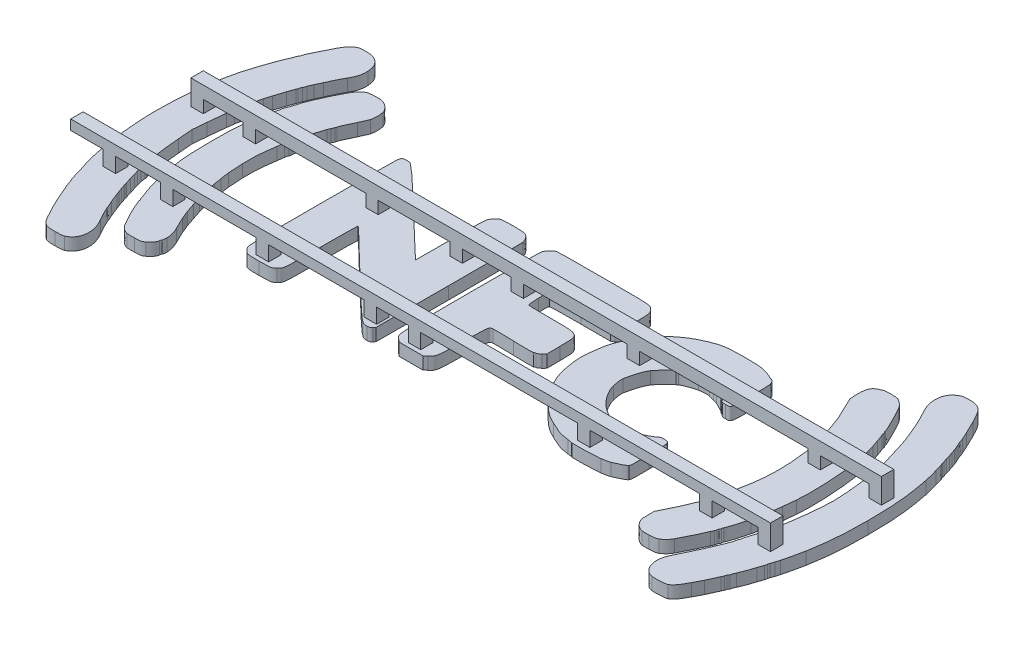
SolidWorks part; units mm, degrees
ref_plane "Front Plane" through (0, 0, 0) normal (0, 0, 1) x (1, 0, 0)
ref_plane "Top Plane" through (0, 0, 0) normal (0, 1, 0) x (1, 0, 0)
ref_plane "Right Plane" through (0, 0, 0) normal (1, 0, 0) x (0, 0, -1)
sketch "Sketch1" plane through (0, 0, 0) normal (0, 1, 0) x (1, 0, 0)
  line L0 (-25.791, 1.2525) -> (-25.8929, 0.1309)
  line L1 (-25.8929, 0.1309) -> (-25.7919, -1.0396)
  line L2 (-20.2822, -5.9651) -> (-20.1846, -6.209)
  line L3 (19.3174, -8.3866) -> (19.3174, -7.8605)
  line L4 (19.3174, -7.8605) -> (19.6062, -7.2786)
  line L5 (-4.6879, -0.4386) -> (-4.7008, -6.2262)
  line L6 (-4.7008, -6.2262) -> (-4.8033, -6.3639)
  line L7 (4.937, 3.3673) -> (4.7167, 3.2276)
  line L8 (4.7167, 3.2276) -> (2.3283, 3.2276)
  line L9 (4.0185, -0.1608) -> (4.0287, -1.2053)
  line L10 (4.0287, -1.2053) -> (3.8359, -1.4029)
  line L11 (-0.6117, -6.1322) -> (-0.8375, -6.3309)
  line L12 (-0.8375, -6.3309) -> (-1.7991, -6.3309)
  line L13 (-1.7991, -6.3309) -> (-2.7607, -6.3309)
  line L14 (-2.7607, -6.3309) -> (-2.984, -6.1344)
  spline S0 degree 3 poles (23.7309, -12.4824) (23.4889, -12.4372) (23.3769, -12.3762) (23.2111, -12.1995) knots 0 0 0 0 1 1 1 1
  spline S1 degree 3 poles (23.2111, -12.1995) (22.8803, -11.8469) (22.7603, -11.3214) (22.882, -10.7588) knots 0 0 0 0 1 1 1 1
  spline S2 degree 3 poles (22.882, -10.7588) (22.9222, -10.5726) (23.1035, -10.1448) (23.3426, -9.6715) knots 0 0 0 0 1 1 1 1
  spline S3 degree 3 poles (23.3426, -9.6715) (23.5595, -9.2424) (23.7938, -8.7482) (23.8633, -8.5735) knots 0 0 0 0 1 1 1 1
  spline S4 degree 3 poles (23.8633, -8.5735) (23.9327, -8.3987) (24.0453, -8.1354) (24.1133, -7.9883) knots 0 0 0 0 1 1 1 1
  spline S5 degree 3 poles (24.1133, -7.9883) (24.4127, -7.3412) (24.6314, -6.7521) (24.6324, -6.5898) knots 0 0 0 0 1 1 1 1
  spline S6 degree 3 poles (24.6324, -6.5898) (24.6329, -6.5311) (24.6551, -6.4694) (24.6819, -6.4528) knots 0 0 0 0 1 1 1 1
  spline S7 degree 3 poles (24.6819, -6.4528) (24.7087, -6.4363) (24.7307, -6.3702) (24.7307, -6.3059) knots 0 0 0 0 1 1 1 1
  spline S8 degree 3 poles (24.7307, -6.3059) (24.7307, -6.2417) (24.7503, -6.1388) (24.7744, -6.0772) knots 0 0 0 0 1 1 1 1
  spline S9 degree 3 poles (24.7744, -6.0772) (24.7984, -6.0156) (24.8455, -5.8664) (24.8789, -5.7457) knots 0 0 0 0 1 1 1 1
  spline S10 degree 3 poles (24.8789, -5.7457) (24.9124, -5.625) (24.9791, -5.3946) (25.0272, -5.2336) knots 0 0 0 0 1 1 1 1
  spline S11 degree 3 poles (25.0272, -5.2336) (25.2177, -4.5958) (25.3159, -4.1859) (25.3159, -4.0284) knots 0 0 0 0 1 1 1 1
  spline S12 degree 3 poles (25.3159, -4.0284) (25.3159, -3.9376) (25.3357, -3.8424) (25.3599, -3.8169) knots 0 0 0 0 1 1 1 1
  spline S13 degree 3 poles (25.3599, -3.8169) (25.3842, -3.7914) (25.4159, -3.6718) (25.4304, -3.5511) knots 0 0 0 0 1 1 1 1
  spline S14 degree 3 poles (25.4304, -3.5511) (25.4449, -3.4304) (25.4801, -3.189) (25.5086, -3.0147) knots 0 0 0 0 1 1 1 1
  spline S15 degree 3 poles (25.5086, -3.0147) (25.6663, -2.0497) (25.7983, -0.6495) (25.8006, 0.0821) knots 0 0 0 0 1 1 1 1
  spline S16 degree 3 poles (25.8006, 0.0821) (25.8022, 0.6103) (25.7166, 1.7106) (25.6032, 2.618) knots 0 0 0 0 1 1 1 1
  spline S17 degree 3 poles (25.6032, 2.618) (25.5798, 2.8058) (25.547, 3.0911) (25.5305, 3.252) knots 0 0 0 0 1 1 1 1
  spline S18 degree 3 poles (25.5305, 3.252) (25.5139, 3.4129) (25.4808, 3.5655) (25.4569, 3.5909) knots 0 0 0 0 1 1 1 1
  spline S19 degree 3 poles (25.4569, 3.5909) (25.433, 3.6164) (25.4134, 3.7136) (25.4134, 3.8069) knots 0 0 0 0 1 1 1 1
  spline S20 degree 3 poles (25.4134, 3.8069) (25.4134, 3.9003) (25.393, 4.044) (25.368, 4.1264) knots 0 0 0 0 1 1 1 1
  spline S21 degree 3 poles (25.368, 4.1264) (25.343, 4.2087) (25.2991, 4.3694) (25.2704, 4.4834) knots 0 0 0 0 1 1 1 1
  spline S22 degree 3 poles (25.2704, 4.4834) (25.2418, 4.5974) (25.1947, 4.7839) (25.1658, 4.8979) knots 0 0 0 0 1 1 1 1
  spline S23 degree 3 poles (25.1658, 4.8979) (25.0819, 5.2284) (24.7658, 6.2579) (24.6828, 6.4707) knots 0 0 0 0 1 1 1 1
  spline S24 degree 3 poles (24.6828, 6.4707) (24.6619, 6.5243) (24.5942, 6.7328) (24.5324, 6.934) knots 0 0 0 0 1 1 1 1
  spline S25 degree 3 poles (24.5324, 6.934) (24.4705, 7.1352) (24.4049, 7.3217) (24.3866, 7.3485) knots 0 0 0 0 1 1 1 1
  spline S26 degree 3 poles (24.3866, 7.3485) (24.3683, 7.3753) (24.3249, 7.4851) (24.2904, 7.5924) knots 0 0 0 0 1 1 1 1
  spline S27 degree 3 poles (24.2904, 7.5924) (24.2558, 7.6996) (24.1541, 7.944) (24.0645, 8.1354) knots 0 0 0 0 1 1 1 1
  spline S28 degree 3 poles (24.0645, 8.1354) (23.9749, 8.3267) (23.9016, 8.4952) (23.9016, 8.5098) knots 0 0 0 0 1 1 1 1
  spline S29 degree 3 poles (23.9016, 8.5098) (23.9016, 8.5733) (23.5285, 9.3385) (23.2908, 9.7625) knots 0 0 0 0 1 1 1 1
  spline S30 degree 3 poles (23.2908, 9.7625) (22.9619, 10.3492) (22.8287, 10.7565) (22.8287, 11.176) knots 0 0 0 0 1 1 1 1
  spline S31 degree 3 poles (22.8287, 11.176) (22.8287, 11.8116) (23.0562, 12.2205) (23.5548, 12.4813) knots 0 0 0 0 1 1 1 1
  spline S32 degree 3 poles (23.5548, 12.4813) (23.7291, 12.5725) (23.8422, 12.5911) (24.2238, 12.5911) knots 0 0 0 0 1 1 1 1
  spline S33 degree 3 poles (24.2238, 12.5911) (25.0642, 12.5911) (25.3016, 12.3941) (25.9022, 11.1988) knots 0 0 0 0 1 1 1 1
  spline S34 degree 3 poles (25.9022, 11.1988) (26.1306, 10.7441) (26.3583, 10.2734) (26.4081, 10.1527) knots 0 0 0 0 1 1 1 1
  spline S35 degree 3 poles (26.4081, 10.1527) (26.4579, 10.032) (26.5617, 9.7984) (26.6388, 9.6336) knots 0 0 0 0 1 1 1 1
  spline S36 degree 3 poles (26.6388, 9.6336) (26.7159, 9.4689) (26.7789, 9.3118) (26.7789, 9.2847) knots 0 0 0 0 1 1 1 1
  spline S37 degree 3 poles (26.7789, 9.2847) (26.7789, 9.2575) (26.8259, 9.14) (26.8834, 9.0234) knots 0 0 0 0 1 1 1 1
  spline S38 degree 3 poles (26.8834, 9.0234) (26.9409, 8.9069) (27.0067, 8.7622) (27.0297, 8.7018) knots 0 0 0 0 1 1 1 1
  spline S39 degree 3 poles (27.0297, 8.7018) (27.0527, 8.6415) (27.092, 8.5427) (27.1171, 8.4824) knots 0 0 0 0 1 1 1 1
  spline S40 degree 3 poles (27.1171, 8.4824) (27.1421, 8.422) (27.1891, 8.2849) (27.2214, 8.1776) knots 0 0 0 0 1 1 1 1
  spline S41 degree 3 poles (27.2214, 8.1776) (27.2537, 8.0703) (27.2965, 7.9386) (27.3166, 7.885) knots 0 0 0 0 1 1 1 1
  spline S42 degree 3 poles (27.3166, 7.885) (27.3366, 7.8313) (27.3796, 7.6887) (27.4121, 7.568) knots 0 0 0 0 1 1 1 1
  spline S43 degree 3 poles (27.4121, 7.568) (27.4446, 7.4473) (27.491, 7.3104) (27.5152, 7.2638) knots 0 0 0 0 1 1 1 1
  spline S44 degree 3 poles (27.5152, 7.2638) (27.5394, 7.2173) (27.5592, 7.1363) (27.5592, 7.0838) knots 0 0 0 0 1 1 1 1
  spline S45 degree 3 poles (27.5592, 7.0838) (27.5592, 7.0314) (27.5786, 6.9765) (27.6024, 6.9618) knots 0 0 0 0 1 1 1 1
  spline S46 degree 3 poles (27.6024, 6.9618) (27.6261, 6.9472) (27.6566, 6.8746) (27.6702, 6.8005) knots 0 0 0 0 1 1 1 1
  spline S47 degree 3 poles (27.6702, 6.8005) (27.6838, 6.7264) (27.7426, 6.5121) (27.8007, 6.3244) knots 0 0 0 0 1 1 1 1
  spline S48 degree 3 poles (27.8007, 6.3244) (27.9324, 5.8995) (28.0161, 5.5767) (28.0884, 5.2149) knots 0 0 0 0 1 1 1 1
  spline S49 degree 3 poles (28.0884, 5.2149) (28.4447, 3.4319) (28.5592, 2.1824) (28.5584, 0.0821) knots 0 0 0 0 1 1 1 1
  spline S50 degree 3 poles (28.5584, 0.0821) (28.5578, -1.7679) (28.4513, -3.0859) (28.1859, -4.5265) knots 0 0 0 0 1 1 1 1
  spline S51 degree 3 poles (28.1859, -4.5265) (28.1002, -4.992) (27.8698, -6.0003) (27.8071, -6.1846) knots 0 0 0 0 1 1 1 1
  spline S52 degree 3 poles (27.8071, -6.1846) (27.7843, -6.2517) (27.739, -6.4053) (27.7064, -6.526) knots 0 0 0 0 1 1 1 1
  spline S53 degree 3 poles (27.7064, -6.526) (27.6739, -6.6467) (27.6275, -6.7835) (27.6032, -6.8301) knots 0 0 0 0 1 1 1 1
  spline S54 degree 3 poles (27.6032, -6.8301) (27.579, -6.8767) (27.5592, -6.9593) (27.5592, -7.0137) knots 0 0 0 0 1 1 1 1
  spline S55 degree 3 poles (27.5592, -7.0137) (27.5592, -7.068) (27.5395, -7.1506) (27.5155, -7.1972) knots 0 0 0 0 1 1 1 1
  spline S56 degree 3 poles (27.5155, -7.1972) (27.4914, -7.2438) (27.4229, -7.4465) (27.3632, -7.6476) knots 0 0 0 0 1 1 1 1
  spline S57 degree 3 poles (27.3632, -7.6476) (27.2304, -8.0955) (27.098, -8.4537) (26.9168, -8.8559) knots 0 0 0 0 1 1 1 1
  spline S58 degree 3 poles (26.9168, -8.8559) (26.841, -9.0242) (26.7789, -9.1943) (26.7789, -9.2338) knots 0 0 0 0 1 1 1 1
  spline S59 degree 3 poles (26.7789, -9.2338) (26.7789, -9.2734) (26.757, -9.3058) (26.7302, -9.3058) knots 0 0 0 0 1 1 1 1
  spline S60 degree 3 poles (26.7302, -9.3058) (26.7034, -9.3058) (26.6814, -9.339) (26.6814, -9.3796) knots 0 0 0 0 1 1 1 1
  spline S61 degree 3 poles (26.6814, -9.3796) (26.6814, -9.4202) (26.662, -9.4915) (26.6383, -9.5381) knots 0 0 0 0 1 1 1 1
  spline S62 degree 3 poles (26.6383, -9.5381) (26.6146, -9.5846) (26.5729, -9.6776) (26.5456, -9.7447) knots 0 0 0 0 1 1 1 1
  spline S63 degree 3 poles (26.5456, -9.7447) (26.4612, -9.9516) (26.1925, -10.5445) (26.141, -10.6372) knots 0 0 0 0 1 1 1 1
  spline S64 degree 3 poles (26.141, -10.6372) (26.1142, -10.6855) (25.9489, -11.0037) (25.7736, -11.3443) knots 0 0 0 0 1 1 1 1
  spline S65 degree 3 poles (25.7736, -11.3443) (25.4563, -11.961) (25.2177, -12.2738) (24.9622, -12.4079) knots 0 0 0 0 1 1 1 1
  spline S66 degree 3 poles (24.9622, -12.4079) (24.8069, -12.4894) (24.0226, -12.5368) (23.7309, -12.4824) knots 0 0 0 0 1 1 1 1
  spline S67 degree 3 poles (-25.0683, -12.3776) (-25.3552, -12.2259) (-25.5554, -11.9292) (-26.106, -10.8391) knots 0 0 0 0 1 1 1 1
  spline S68 degree 3 poles (-26.106, -10.8391) (-26.2423, -10.5693) (-26.3953, -10.251) (-26.446, -10.1319) knots 0 0 0 0 1 1 1 1
  spline S69 degree 3 poles (-26.446, -10.1319) (-26.4967, -10.0128) (-26.579, -9.8289) (-26.6289, -9.7233) knots 0 0 0 0 1 1 1 1
  spline S70 degree 3 poles (-26.6289, -9.7233) (-26.6788, -9.6177) (-26.7196, -9.5139) (-26.7196, -9.4926) knots 0 0 0 0 1 1 1 1
  spline S71 degree 3 poles (-26.7196, -9.4926) (-26.7196, -9.4713) (-26.8073, -9.2692) (-26.9146, -9.0434) knots 0 0 0 0 1 1 1 1
  spline S72 degree 3 poles (-26.9146, -9.0434) (-27.0219, -8.8175) (-27.1097, -8.6083) (-27.1097, -8.5785) knots 0 0 0 0 1 1 1 1
  spline S73 degree 3 poles (-27.1097, -8.5785) (-27.1097, -8.5486) (-27.1291, -8.486) (-27.1528, -8.4395) knots 0 0 0 0 1 1 1 1
  spline S74 degree 3 poles (-27.1528, -8.4395) (-27.2578, -8.233) (-27.4259, -7.7333) (-27.5012, -7.4038) knots 0 0 0 0 1 1 1 1
  spline S75 degree 3 poles (-27.5012, -7.4038) (-27.5227, -7.3099) (-27.6108, -7.0356) (-27.6971, -6.7942) knots 0 0 0 0 1 1 1 1
  spline S76 degree 3 poles (-27.6971, -6.7942) (-27.8572, -6.3461) (-27.8997, -6.1991) (-27.9931, -5.7701) knots 0 0 0 0 1 1 1 1
  spline S77 degree 3 poles (-27.9931, -5.7701) (-28.0222, -5.636) (-28.0659, -5.4385) (-28.0901, -5.3312) knots 0 0 0 0 1 1 1 1
  spline S78 degree 3 poles (-28.0901, -5.3312) (-28.3344, -4.2476) (-28.5001, -3.0568) (-28.5983, -1.6791) knots 0 0 0 0 1 1 1 1
  spline S79 degree 3 poles (-28.5983, -1.6791) (-28.7462, 0.3952) (-28.6303, 2.6453) (-28.2765, 4.5687) knots 0 0 0 0 1 1 1 1
  spline S80 degree 3 poles (-28.2765, 4.5687) (-28.2469, 4.7297) (-28.2045, 4.9601) (-28.1821, 5.0808) knots 0 0 0 0 1 1 1 1
  spline S81 degree 3 poles (-28.1821, 5.0808) (-28.0598, 5.7425) (-27.9029, 6.3253) (-27.6177, 7.1778) knots 0 0 0 0 1 1 1 1
  spline S82 degree 3 poles (-27.6177, 7.1778) (-27.4427, 7.7009) (-27.2809, 8.1727) (-27.2583, 8.2263) knots 0 0 0 0 1 1 1 1
  spline S83 degree 3 poles (-27.2583, 8.2263) (-27.2356, 8.28) (-27.1905, 8.4007) (-27.1579, 8.4946) knots 0 0 0 0 1 1 1 1
  spline S84 degree 3 poles (-27.1579, 8.4946) (-27.1254, 8.5884) (-27.0354, 8.8034) (-26.9579, 8.9722) knots 0 0 0 0 1 1 1 1
  spline S85 degree 3 poles (-26.9579, 8.9722) (-26.8805, 9.1411) (-26.8171, 9.2995) (-26.8171, 9.3243) knots 0 0 0 0 1 1 1 1
  spline S86 degree 3 poles (-26.8171, 9.3243) (-26.8171, 9.3491) (-26.7732, 9.4476) (-26.7196, 9.5431) knots 0 0 0 0 1 1 1 1
  spline S87 degree 3 poles (-26.7196, 9.5431) (-26.6659, 9.6386) (-26.622, 9.7459) (-26.622, 9.7815) knots 0 0 0 0 1 1 1 1
  spline S88 degree 3 poles (-26.622, 9.7815) (-26.622, 9.8172) (-26.5576, 9.9756) (-26.4789, 10.1336) knots 0 0 0 0 1 1 1 1
  spline S89 degree 3 poles (-26.4789, 10.1336) (-26.4002, 10.2916) (-26.2464, 10.6074) (-26.137, 10.8354) knots 0 0 0 0 1 1 1 1
  spline S90 degree 3 poles (-26.137, 10.8354) (-25.5801, 11.9967) (-25.3831, 12.2843) (-25.0064, 12.4854) knots 0 0 0 0 1 1 1 1
  spline S91 degree 3 poles (-25.0064, 12.4854) (-24.8437, 12.5722) (-24.7267, 12.5911) (-24.3511, 12.5911) knots 0 0 0 0 1 1 1 1
  spline S92 degree 3 poles (-24.3511, 12.5911) (-23.8028, 12.5911) (-23.473, 12.4707) (-23.2143, 12.1759) knots 0 0 0 0 1 1 1 1
  spline S93 degree 3 poles (-23.2143, 12.1759) (-22.9928, 11.9237) (-22.9201, 11.732) (-22.884, 11.305) knots 0 0 0 0 1 1 1 1
  spline S94 degree 3 poles (-22.884, 11.305) (-22.847, 10.8668) (-22.9637, 10.4288) (-23.2366, 9.982) knots 0 0 0 0 1 1 1 1
  spline S95 degree 3 poles (-23.2366, 9.982) (-23.3924, 9.7269) (-23.6159, 9.275) (-23.8757, 8.6896) knots 0 0 0 0 1 1 1 1
  spline S96 degree 3 poles (-23.8757, 8.6896) (-23.9173, 8.5958) (-24.0256, 8.3605) (-24.1163, 8.1668) knots 0 0 0 0 1 1 1 1
  spline S97 degree 3 poles (-24.1163, 8.1668) (-24.207, 7.9731) (-24.2812, 7.7961) (-24.2812, 7.7736) knots 0 0 0 0 1 1 1 1
  spline S98 degree 3 poles (-24.2812, 7.7736) (-24.2812, 7.751) (-24.325, 7.6418) (-24.3787, 7.5307) knots 0 0 0 0 1 1 1 1
  spline S99 degree 3 poles (-24.3787, 7.5307) (-24.4323, 7.4197) (-24.4762, 7.2993) (-24.4762, 7.2631) knots 0 0 0 0 1 1 1 1
  spline S100 degree 3 poles (-24.4762, 7.2631) (-24.4762, 7.2269) (-24.4942, 7.1765) (-24.5162, 7.151) knots 0 0 0 0 1 1 1 1
  spline S101 degree 3 poles (-24.5162, 7.151) (-24.5382, 7.1255) (-24.6294, 6.8742) (-24.7189, 6.5926) knots 0 0 0 0 1 1 1 1
  spline S102 degree 3 poles (-24.7189, 6.5926) (-24.8084, 6.311) (-24.9359, 5.916) (-25.0023, 5.7148) knots 0 0 0 0 1 1 1 1
  spline S103 degree 3 poles (-25.0023, 5.7148) (-25.0686, 5.5136) (-25.142, 5.2667) (-25.1653, 5.1661) knots 0 0 0 0 1 1 1 1
  spline S104 degree 3 poles (-25.1653, 5.1661) (-25.1887, 5.0656) (-25.2309, 4.89) (-25.2592, 4.776) knots 0 0 0 0 1 1 1 1
  spline S105 degree 3 poles (-25.2592, 4.776) (-25.3655, 4.3476) (-25.4106, 4.1234) (-25.4333, 3.9104) knots 0 0 0 0 1 1 1 1
  spline S106 degree 3 poles (-25.4333, 3.9104) (-25.4462, 3.7897) (-25.476, 3.647) (-25.4995, 3.5934) knots 0 0 0 0 1 1 1 1
  spline S107 degree 3 poles (-25.4995, 3.5934) (-25.5231, 3.5397) (-25.5561, 3.3751) (-25.5729, 3.2276) knots 0 0 0 0 1 1 1 1
  spline S108 degree 3 poles (-25.5729, 3.2276) (-25.5897, 3.0801) (-25.6227, 2.8277) (-25.6463, 2.6668) knots 0 0 0 0 1 1 1 1
  spline S109 degree 3 poles (-25.6463, 2.6668) (-25.6698, 2.5059) (-25.7349, 1.8694) (-25.791, 1.2525) knots 0 0 0 0 1 1 1 1
  spline S110 degree 3 poles (-25.7919, -1.0396) (-25.6979, -2.1287) (-25.659, -2.4679) (-25.5486, -3.161) knots 0 0 0 0 1 1 1 1
  spline S111 degree 3 poles (-25.5486, -3.161) (-25.5252, -3.3085) (-25.4909, -3.5449) (-25.4725, -3.6863) knots 0 0 0 0 1 1 1 1
  spline S112 degree 3 poles (-25.4725, -3.6863) (-25.454, -3.8276) (-25.4199, -3.9551) (-25.3965, -3.9696) knots 0 0 0 0 1 1 1 1
  spline S113 degree 3 poles (-25.3965, -3.9696) (-25.3732, -3.984) (-25.3541, -4.0862) (-25.3541, -4.1967) knots 0 0 0 0 1 1 1 1
  spline S114 degree 3 poles (-25.3541, -4.1967) (-25.3541, -4.3072) (-25.3336, -4.465) (-25.3086, -4.5474) knots 0 0 0 0 1 1 1 1
  spline S115 degree 3 poles (-25.3086, -4.5474) (-25.2836, -4.6298) (-25.2371, -4.7959) (-25.2054, -4.9166) knots 0 0 0 0 1 1 1 1
  spline S116 degree 3 poles (-25.2054, -4.9166) (-25.1736, -5.0373) (-25.1298, -5.191) (-25.1079, -5.258) knots 0 0 0 0 1 1 1 1
  spline S117 degree 3 poles (-25.1079, -5.258) (-25.086, -5.3251) (-25.0209, -5.5445) (-24.9631, -5.7457) knots 0 0 0 0 1 1 1 1
  spline S118 degree 3 poles (-24.9631, -5.7457) (-24.9054, -5.9469) (-24.838, -6.1496) (-24.8135, -6.1961) knots 0 0 0 0 1 1 1 1
  spline S119 degree 3 poles (-24.8135, -6.1961) (-24.7889, -6.2427) (-24.7688, -6.3143) (-24.7688, -6.3553) knots 0 0 0 0 1 1 1 1
  spline S120 degree 3 poles (-24.7688, -6.3553) (-24.7688, -6.3963) (-24.749, -6.4679) (-24.7248, -6.5145) knots 0 0 0 0 1 1 1 1
  spline S121 degree 3 poles (-24.7248, -6.5145) (-24.7006, -6.561) (-24.6528, -6.6979) (-24.6185, -6.8186) knots 0 0 0 0 1 1 1 1
  spline S122 degree 3 poles (-24.6185, -6.8186) (-24.5842, -6.9393) (-24.5422, -7.06) (-24.525, -7.0868) knots 0 0 0 0 1 1 1 1
  spline S123 degree 3 poles (-24.525, -7.0868) (-24.5078, -7.1136) (-24.4641, -7.2343) (-24.4277, -7.355) knots 0 0 0 0 1 1 1 1
  spline S124 degree 3 poles (-24.4277, -7.355) (-24.3914, -7.4757) (-24.2557, -7.8098) (-24.1263, -8.0974) knots 0 0 0 0 1 1 1 1
  spline S125 degree 3 poles (-24.1263, -8.0974) (-23.9969, -8.385) (-23.891, -8.634) (-23.891, -8.6508) knots 0 0 0 0 1 1 1 1
  spline S126 degree 3 poles (-23.891, -8.6508) (-23.891, -8.718) (-23.4743, -9.5433) (-23.3018, -9.8178) knots 0 0 0 0 1 1 1 1
  spline S127 degree 3 poles (-23.3018, -9.8178) (-22.6245, -10.8954) (-22.763, -12.0521) (-23.6129, -12.4171) knots 0 0 0 0 1 1 1 1
  spline S128 degree 3 poles (-23.6129, -12.4171) (-23.6944, -12.4521) (-23.9791, -12.4748) (-24.32, -12.4735) knots 0 0 0 0 1 1 1 1
  spline S129 degree 3 poles (-24.32, -12.4735) (-24.7863, -12.4718) (-24.9233, -12.4542) (-25.0683, -12.3776) knots 0 0 0 0 1 1 1 1
  spline S130 degree 3 poles (-21.2767, -9.7122) (-21.4914, -9.6755) (-21.7844, -9.4591) (-21.9551, -9.2114) knots 0 0 0 0 1 1 1 1
  spline S131 degree 3 poles (-21.9551, -9.2114) (-22.1191, -8.9732) (-22.8669, -7.526) (-22.8669, -7.4466) knots 0 0 0 0 1 1 1 1
  spline S132 degree 3 poles (-22.8669, -7.4466) (-22.8669, -7.4205) (-22.9108, -7.3082) (-22.9644, -7.1972) knots 0 0 0 0 1 1 1 1
  spline S133 degree 3 poles (-22.9644, -7.1972) (-23.0181, -7.0862) (-23.062, -6.9569) (-23.062, -6.9098) knots 0 0 0 0 1 1 1 1
  spline S134 degree 3 poles (-23.062, -6.9098) (-23.062, -6.8628) (-23.0839, -6.8108) (-23.1107, -6.7942) knots 0 0 0 0 1 1 1 1
  spline S135 degree 3 poles (-23.1107, -6.7942) (-23.1375, -6.7776) (-23.1595, -6.7322) (-23.1595, -6.6933) knots 0 0 0 0 1 1 1 1
  spline S136 degree 3 poles (-23.1595, -6.6933) (-23.1595, -6.6543) (-23.2002, -6.5294) (-23.2499, -6.4157) knots 0 0 0 0 1 1 1 1
  spline S137 degree 3 poles (-23.2499, -6.4157) (-23.4233, -6.0195) (-23.6428, -5.338) (-23.7223, -4.9493) knots 0 0 0 0 1 1 1 1
  spline S138 degree 3 poles (-23.7223, -4.9493) (-23.7324, -4.9002) (-23.7547, -4.8158) (-23.7719, -4.7616) knots 0 0 0 0 1 1 1 1
  spline S139 degree 3 poles (-23.7719, -4.7616) (-23.7891, -4.7074) (-23.8099, -4.6159) (-23.8181, -4.5582) knots 0 0 0 0 1 1 1 1
  spline S140 degree 3 poles (-23.8181, -4.5582) (-23.8263, -4.5005) (-23.8573, -4.3436) (-23.8869, -4.2095) knots 0 0 0 0 1 1 1 1
  spline S141 degree 3 poles (-23.8869, -4.2095) (-23.9164, -4.0754) (-23.9533, -3.8998) (-23.9689, -3.8194) knots 0 0 0 0 1 1 1 1
  spline S142 degree 3 poles (-23.9689, -3.8194) (-23.9844, -3.7389) (-24.0267, -3.5194) (-24.0629, -3.3317) knots 0 0 0 0 1 1 1 1
  spline S143 degree 3 poles (-24.0629, -3.3317) (-24.251, -2.3549) (-24.3028, -1.5967) (-24.3013, 0.1552) knots 0 0 0 0 1 1 1 1
  spline S144 degree 3 poles (-24.3013, 0.1552) (-24.2997, 1.9706) (-24.2627, 2.448) (-24.029, 3.6637) knots 0 0 0 0 1 1 1 1
  spline S145 degree 3 poles (-24.029, 3.6637) (-23.9746, 3.9469) (-23.911, 4.2774) (-23.8878, 4.3981) knots 0 0 0 0 1 1 1 1
  spline S146 degree 3 poles (-23.8878, 4.3981) (-23.8646, 4.5188) (-23.8148, 4.7437) (-23.7772, 4.8979) knots 0 0 0 0 1 1 1 1
  spline S147 degree 3 poles (-23.7772, 4.8979) (-23.7395, 5.0522) (-23.715, 5.1783) (-23.7227, 5.1783) knots 0 0 0 0 1 1 1 1
  spline S148 degree 3 poles (-23.7227, 5.1783) (-23.7303, 5.1783) (-23.6598, 5.3923) (-23.5659, 5.6538) knots 0 0 0 0 1 1 1 1
  spline S149 degree 3 poles (-23.5659, 5.6538) (-23.472, 5.9153) (-23.3783, 6.2061) (-23.3576, 6.3) knots 0 0 0 0 1 1 1 1
  spline S150 degree 3 poles (-23.3576, 6.3) (-23.3369, 6.3939) (-23.2863, 6.5475) (-23.2453, 6.6414) knots 0 0 0 0 1 1 1 1
  spline S151 degree 3 poles (-23.2453, 6.6414) (-23.2043, 6.7353) (-23.1003, 6.9876) (-23.0142, 7.2022) knots 0 0 0 0 1 1 1 1
  spline S152 degree 3 poles (-23.0142, 7.2022) (-22.8292, 7.6635) (-22.3234, 8.7098) (-22.1184, 9.0554) knots 0 0 0 0 1 1 1 1
  spline S153 degree 3 poles (-22.1184, 9.0554) (-21.9264, 9.379) (-21.6624, 9.6545) (-21.4526, 9.7503) knots 0 0 0 0 1 1 1 1
  spline S154 degree 3 poles (-21.4526, 9.7503) (-21.222, 9.8557) (-20.3746, 9.8643) (-20.1359, 9.7638) knots 0 0 0 0 1 1 1 1
  spline S155 degree 3 poles (-20.1359, 9.7638) (-19.8023, 9.6233) (-19.5009, 9.3199) (-19.4165, 9.0399) knots 0 0 0 0 1 1 1 1
  spline S156 degree 3 poles (-19.4165, 9.0399) (-19.3406, 8.7878) (-19.3375, 8.2417) (-19.4107, 8.0104) knots 0 0 0 0 1 1 1 1
  spline S157 degree 3 poles (-19.4107, 8.0104) (-19.441, 7.9146) (-19.5819, 7.5948) (-19.7238, 7.2998) knots 0 0 0 0 1 1 1 1
  spline S158 degree 3 poles (-19.7238, 7.2998) (-20.0636, 6.5931) (-20.2334, 6.2105) (-20.2334, 6.1516) knots 0 0 0 0 1 1 1 1
  spline S159 degree 3 poles (-20.2334, 6.1516) (-20.2334, 6.1252) (-20.2528, 6.0655) (-20.2765, 6.0189) knots 0 0 0 0 1 1 1 1
  spline S160 degree 3 poles (-20.2765, 6.0189) (-20.3002, 5.9724) (-20.3411, 5.8794) (-20.3675, 5.8123) knots 0 0 0 0 1 1 1 1
  spline S161 degree 3 poles (-20.3675, 5.8123) (-20.3939, 5.7453) (-20.4387, 5.6355) (-20.4672, 5.5685) knots 0 0 0 0 1 1 1 1
  spline S162 degree 3 poles (-20.4672, 5.5685) (-20.5304, 5.4197) (-20.8838, 4.3111) (-20.9647, 4.0079) knots 0 0 0 0 1 1 1 1
  spline S163 degree 3 poles (-20.9647, 4.0079) (-20.9969, 3.8872) (-21.043, 3.7503) (-21.0672, 3.7038) knots 0 0 0 0 1 1 1 1
  spline S164 degree 3 poles (-21.0672, 3.7038) (-21.0914, 3.6572) (-21.1112, 3.5323) (-21.1112, 3.4262) knots 0 0 0 0 1 1 1 1
  spline S165 degree 3 poles (-21.1112, 3.4262) (-21.1112, 3.3202) (-21.1303, 3.2216) (-21.1537, 3.2071) knots 0 0 0 0 1 1 1 1
  spline S166 degree 3 poles (-21.1537, 3.2071) (-21.1771, 3.1927) (-21.2114, 3.0652) (-21.2299, 2.9238) knots 0 0 0 0 1 1 1 1
  spline S167 degree 3 poles (-21.2299, 2.9238) (-21.2485, 2.7825) (-21.2818, 2.5351) (-21.3039, 2.3742) knots 0 0 0 0 1 1 1 1
  spline S168 degree 3 poles (-21.3039, 2.3742) (-21.4829, 1.0699) (-21.5094, 0.6897) (-21.4825, -0.1861) knots 0 0 0 0 1 1 1 1
  spline S169 degree 3 poles (-21.4825, -0.1861) (-21.4673, -0.6823) (-21.4339, -1.231) (-21.4084, -1.4053) knots 0 0 0 0 1 1 1 1
  spline S170 degree 3 poles (-21.4084, -1.4053) (-21.3828, -1.5797) (-21.3379, -1.8979) (-21.3086, -2.1125) knots 0 0 0 0 1 1 1 1
  spline S171 degree 3 poles (-21.3086, -2.1125) (-21.2792, -2.327) (-21.2326, -2.6123) (-21.205, -2.7465) knots 0 0 0 0 1 1 1 1
  spline S172 degree 3 poles (-21.205, -2.7465) (-21.1774, -2.8806) (-21.136, -3.1) (-21.1131, -3.2341) knots 0 0 0 0 1 1 1 1
  spline S173 degree 3 poles (-21.1131, -3.2341) (-21.0901, -3.3682) (-21.0456, -3.5658) (-21.0141, -3.673) knots 0 0 0 0 1 1 1 1
  spline S174 degree 3 poles (-21.0141, -3.673) (-20.9826, -3.7803) (-20.9462, -3.934) (-20.9332, -4.0144) knots 0 0 0 0 1 1 1 1
  spline S175 degree 3 poles (-20.9332, -4.0144) (-20.9202, -4.0949) (-20.8918, -4.2046) (-20.8702, -4.2583) knots 0 0 0 0 1 1 1 1
  spline S176 degree 3 poles (-20.8702, -4.2583) (-20.8486, -4.3119) (-20.7394, -4.6411) (-20.6277, -4.9898) knots 0 0 0 0 1 1 1 1
  spline S177 degree 3 poles (-20.6277, -4.9898) (-20.5159, -5.3385) (-20.4034, -5.6731) (-20.3777, -5.7335) knots 0 0 0 0 1 1 1 1
  spline S178 degree 3 poles (-20.3777, -5.7335) (-20.352, -5.7938) (-20.309, -5.8981) (-20.2822, -5.9651) knots 0 0 0 0 1 1 1 1
  spline S179 degree 3 poles (-20.1846, -6.209) (-20.1578, -6.276) (-20.1168, -6.3803) (-20.0935, -6.4406) knots 0 0 0 0 1 1 1 1
  spline S180 degree 3 poles (-20.0935, -6.4406) (-20.0508, -6.5514) (-19.8454, -6.971) (-19.658, -7.3306) knots 0 0 0 0 1 1 1 1
  spline S181 degree 3 poles (-19.658, -7.3306) (-19.4739, -7.6839) (-19.3556, -8.1084) (-19.3556, -8.4161) knots 0 0 0 0 1 1 1 1
  spline S182 degree 3 poles (-19.3556, -8.4161) (-19.3556, -8.5804) (-19.3775, -8.7283) (-19.4044, -8.7449) knots 0 0 0 0 1 1 1 1
  spline S183 degree 3 poles (-19.4044, -8.7449) (-19.4312, -8.7615) (-19.4531, -8.8291) (-19.4531, -8.8951) knots 0 0 0 0 1 1 1 1
  spline S184 degree 3 poles (-19.4531, -8.8951) (-19.4531, -9.0768) (-19.6671, -9.378) (-19.9195, -9.5517) knots 0 0 0 0 1 1 1 1
  spline S185 degree 3 poles (-19.9195, -9.5517) (-20.1314, -9.6975) (-20.175, -9.7078) (-20.6403, -9.7217) knots 0 0 0 0 1 1 1 1
  spline S186 degree 3 poles (-20.6403, -9.7217) (-20.9127, -9.7298) (-21.1991, -9.7256) (-21.2767, -9.7122) knots 0 0 0 0 1 1 1 1
  spline S187 degree 3 poles (20.1709, -9.7145) (19.8457, -9.6303) (19.6058, -9.4331) (19.4196, -9.097) knots 0 0 0 0 1 1 1 1
  spline S188 degree 3 poles (19.4196, -9.097) (19.3336, -8.9418) (19.3174, -8.8294) (19.3174, -8.3866) knots 0 0 0 0 1 1 1 1
  spline S189 degree 3 poles (19.6062, -7.2786) (19.9172, -6.6518) (20.1405, -6.1643) (20.2412, -5.892) knots 0 0 0 0 1 1 1 1
  spline S190 degree 3 poles (20.2412, -5.892) (20.2759, -5.7981) (20.3456, -5.6283) (20.3961, -5.5146) knots 0 0 0 0 1 1 1 1
  spline S191 degree 3 poles (20.3961, -5.5146) (20.4466, -5.4009) (20.4879, -5.265) (20.4879, -5.2126) knots 0 0 0 0 1 1 1 1
  spline S192 degree 3 poles (20.4879, -5.2126) (20.4879, -5.1603) (20.5073, -5.1055) (20.531, -5.0908) knots 0 0 0 0 1 1 1 1
  spline S193 degree 3 poles (20.531, -5.0908) (20.5547, -5.0761) (20.5853, -5.0035) (20.5989, -4.9294) knots 0 0 0 0 1 1 1 1
  spline S194 degree 3 poles (20.5989, -4.9294) (20.6125, -4.8553) (20.6717, -4.6411) (20.7304, -4.4533) knots 0 0 0 0 1 1 1 1
  spline S195 degree 3 poles (20.7304, -4.4533) (20.9916, -3.6188) (21.0644, -3.2938) (21.2706, -2.0393) knots 0 0 0 0 1 1 1 1
  spline S196 degree 3 poles (21.2706, -2.0393) (21.4909, -0.6993) (21.4891, 0.8157) (21.2656, 2.3498) knots 0 0 0 0 1 1 1 1
  spline S197 degree 3 poles (21.2656, 2.3498) (21.2402, 2.5241) (21.2057, 2.7824) (21.1889, 2.9237) knots 0 0 0 0 1 1 1 1
  spline S198 degree 3 poles (21.1889, 2.9237) (21.1721, 3.065) (21.1392, 3.1925) (21.1157, 3.207) knots 0 0 0 0 1 1 1 1
  spline S199 degree 3 poles (21.1157, 3.207) (21.0923, 3.2215) (21.0731, 3.3019) (21.0731, 3.3855) knots 0 0 0 0 1 1 1 1
  spline S200 degree 3 poles (21.0731, 3.3855) (21.0731, 3.4692) (21.0511, 3.6051) (21.0243, 3.6875) knots 0 0 0 0 1 1 1 1
  spline S201 degree 3 poles (21.0243, 3.6875) (20.6176, 4.9357) (20.3631, 5.6775) (20.2878, 5.8337) knots 0 0 0 0 1 1 1 1
  spline S202 degree 3 poles (20.2878, 5.8337) (20.2369, 5.9393) (20.1953, 6.0471) (20.1953, 6.0733) knots 0 0 0 0 1 1 1 1
  spline S203 degree 3 poles (20.1953, 6.0733) (20.1953, 6.1113) (19.5476, 7.4717) (19.3621, 7.8233) knots 0 0 0 0 1 1 1 1
  spline S204 degree 3 poles (19.3621, 7.8233) (19.3375, 7.8699) (19.3174, 8.1676) (19.3174, 8.4847) knots 0 0 0 0 1 1 1 1
  spline S205 degree 3 poles (19.3174, 8.4847) (19.3174, 9.2956) (19.4433, 9.5159) (20.049, 9.7654) knots 0 0 0 0 1 1 1 1
  spline S206 degree 3 poles (20.049, 9.7654) (20.28, 9.8606) (21.1482, 9.8564) (21.3169, 9.7593) knots 0 0 0 0 1 1 1 1
  spline S207 degree 3 poles (21.3169, 9.7593) (21.5941, 9.5997) (21.777, 9.4309) (21.9473, 9.1773) knots 0 0 0 0 1 1 1 1
  spline S208 degree 3 poles (21.9473, 9.1773) (22.1673, 8.8499) (23.0238, 7.1342) (23.0238, 7.0211) knots 0 0 0 0 1 1 1 1
  spline S209 degree 3 poles (23.0238, 7.0211) (23.0238, 6.9764) (23.0457, 6.9262) (23.0726, 6.9096) knots 0 0 0 0 1 1 1 1
  spline S210 degree 3 poles (23.0726, 6.9096) (23.0994, 6.893) (23.1213, 6.8366) (23.1213, 6.7841) knots 0 0 0 0 1 1 1 1
  spline S211 degree 3 poles (23.1213, 6.7841) (23.1213, 6.7317) (23.1407, 6.6507) (23.1644, 6.6041) knots 0 0 0 0 1 1 1 1
  spline S212 degree 3 poles (23.1644, 6.6041) (23.2349, 6.4655) (23.3013, 6.2903) (23.3811, 6.0318) knots 0 0 0 0 1 1 1 1
  spline S213 degree 3 poles (23.3811, 6.0318) (23.4225, 5.8977) (23.5047, 5.6563) (23.5639, 5.4953) knots 0 0 0 0 1 1 1 1
  spline S214 degree 3 poles (23.5639, 5.4953) (23.623, 5.3344) (23.6881, 5.1259) (23.7085, 5.032) knots 0 0 0 0 1 1 1 1
  spline S215 degree 3 poles (23.7085, 5.032) (23.8189, 4.523) (23.8673, 4.3058) (23.9096, 4.1298) knots 0 0 0 0 1 1 1 1
  spline S216 degree 3 poles (23.9096, 4.1298) (24.2095, 2.8827) (24.3839, 0.0174) (24.2432, -1.3483) knots 0 0 0 0 1 1 1 1
  spline S217 degree 3 poles (24.2432, -1.3483) (24.2164, -1.6076) (24.1707, -2.0613) (24.1417, -2.3563) knots 0 0 0 0 1 1 1 1
  spline S218 degree 3 poles (24.1417, -2.3563) (24.0647, -3.1373) (23.9873, -3.5996) (23.7785, -4.5265) knots 0 0 0 0 1 1 1 1
  spline S219 degree 3 poles (23.7785, -4.5265) (23.6588, -5.0582) (23.3652, -6.013) (23.2651, -6.1961) knots 0 0 0 0 1 1 1 1
  spline S220 degree 3 poles (23.2651, -6.1961) (23.2397, -6.2427) (23.2189, -6.3237) (23.2189, -6.3761) knots 0 0 0 0 1 1 1 1
  spline S221 degree 3 poles (23.2189, -6.3761) (23.2189, -6.4286) (23.1969, -6.485) (23.1701, -6.5016) knots 0 0 0 0 1 1 1 1
  spline S222 degree 3 poles (23.1701, -6.5016) (23.1433, -6.5182) (23.1213, -6.5809) (23.1213, -6.641) knots 0 0 0 0 1 1 1 1
  spline S223 degree 3 poles (23.1213, -6.641) (23.1213, -6.7011) (23.1029, -6.7712) (23.0804, -6.7966) knots 0 0 0 0 1 1 1 1
  spline S224 degree 3 poles (23.0804, -6.7966) (23.0579, -6.8221) (23.0116, -6.9198) (22.9776, -7.0137) knots 0 0 0 0 1 1 1 1
  spline S225 degree 3 poles (22.9776, -7.0137) (22.8758, -7.2948) (22.3992, -8.2839) (22.0403, -8.9589) knots 0 0 0 0 1 1 1 1
  spline S226 degree 3 poles (22.0403, -8.9589) (21.8952, -9.232) (21.6862, -9.453) (21.4388, -9.5952) knots 0 0 0 0 1 1 1 1
  spline S227 degree 3 poles (21.4388, -9.5952) (21.2786, -9.6874) (21.1567, -9.7103) (20.7561, -9.7236) knots 0 0 0 0 1 1 1 1
  spline S228 degree 3 poles (20.7561, -9.7236) (20.4879, -9.7325) (20.2245, -9.7284) (20.1709, -9.7145) knots 0 0 0 0 1 1 1 1
  spline S229 degree 3 poles (-5.603, -6.3856) (-5.7237, -6.3062) (-5.94, -6.1298) (-6.0837, -5.9935) knots 0 0 0 0 1 1 1 1
  spline S230 degree 3 poles (-6.0837, -5.9935) (-6.2273, -5.8572) (-6.3517, -5.7457) (-6.3601, -5.7457) knots 0 0 0 0 1 1 1 1
  spline S231 degree 3 poles (-6.3601, -5.7457) (-6.3686, -5.7457) (-6.7009, -5.4313) (-7.0987, -5.0471) knots 0 0 0 0 1 1 1 1
  spline S232 degree 3 poles (-7.0987, -5.0471) (-8.0491, -4.1292) (-9.0499, -3.1723) (-9.5041, -2.7471) knots 0 0 0 0 1 1 1 1
  spline S233 degree 3 poles (-9.5041, -2.7471) (-9.7051, -2.559) (-10.2304, -2.054) (-10.6714, -1.6248) knots 0 0 0 0 1 1 1 1
  spline S234 degree 3 poles (-10.6714, -1.6248) (-12.2991, -0.0407) (-12.4498, 0.1003) (-12.4885, 0.0764) knots 0 0 0 0 1 1 1 1
  spline S235 degree 3 poles (-12.4885, 0.0764) (-12.5103, 0.0629) (-12.5281, -1.2279) (-12.5281, -2.7922) knots 0 0 0 0 1 1 1 1
  spline S236 degree 3 poles (-12.5281, -2.7922) (-12.5281, -5.8871) (-12.5235, -5.8326) (-12.8045, -6.0933) knots 0 0 0 0 1 1 1 1
  spline S237 degree 3 poles (-12.8045, -6.0933) (-13.0473, -6.3186) (-13.1109, -6.3309) (-14.0327, -6.3309) knots 0 0 0 0 1 1 1 1
  spline S238 degree 3 poles (-14.0327, -6.3309) (-14.991, -6.3309) (-15.0701, -6.3121) (-15.3002, -6.03) knots 0 0 0 0 1 1 1 1
  spline S239 degree 3 poles (-15.3002, -6.03) (-15.5908, -5.6738) (-15.5784, -5.9626) (-15.5692, 0.2268) knots 0 0 0 0 1 1 1 1
  spline S240 degree 3 poles (-15.5692, 0.2268) (-15.5646, 3.3374) (-15.5455, 6.0249) (-15.5268, 6.1992) knots 0 0 0 0 1 1 1 1
  spline S241 degree 3 poles (-15.5268, 6.1992) (-15.5048, 6.4048) (-15.4647, 6.5375) (-15.4126, 6.5772) knots 0 0 0 0 1 1 1 1
  spline S242 degree 3 poles (-15.4126, 6.5772) (-15.3084, 6.6564) (-14.9686, 6.6582) (-14.7848, 6.5804) knots 0 0 0 0 1 1 1 1
  spline S243 degree 3 poles (-14.7848, 6.5804) (-14.6091, 6.5061) (-13.579, 5.5732) (-12.4828, 4.4956) knots 0 0 0 0 1 1 1 1
  spline S244 degree 3 poles (-12.4828, 4.4956) (-12.2509, 4.2676) (-11.789, 3.8287) (-11.4564, 3.5202) knots 0 0 0 0 1 1 1 1
  spline S245 degree 3 poles (-11.4564, 3.5202) (-11.1238, 3.2118) (-10.7185, 2.8277) (-10.5558, 2.6668) knots 0 0 0 0 1 1 1 1
  spline S246 degree 3 poles (-10.5558, 2.6668) (-10.3931, 2.5059) (-9.876, 2.0099) (-9.4067, 1.5647) knots 0 0 0 0 1 1 1 1
  spline S247 degree 3 poles (-9.4067, 1.5647) (-8.9374, 1.1195) (-8.3896, 0.5983) (-8.1892, 0.4065) knots 0 0 0 0 1 1 1 1
  spline S248 degree 3 poles (-8.1892, 0.4065) (-7.9889, 0.2147) (-7.8188, 0.0577) (-7.8113, 0.0577) knots 0 0 0 0 1 1 1 1
  spline S249 degree 3 poles (-7.8113, 0.0577) (-7.8037, 0.0577) (-7.7976, 1.2786) (-7.7976, 2.7709) knots 0 0 0 0 1 1 1 1
  spline S250 degree 3 poles (-7.7976, 2.7709) (-7.7976, 4.6897) (-7.7809, 5.5428) (-7.7407, 5.6848) knots 0 0 0 0 1 1 1 1
  spline S251 degree 3 poles (-7.7407, 5.6848) (-7.6787, 5.9038) (-7.4588, 6.1711) (-7.2514, 6.2798) knots 0 0 0 0 1 1 1 1
  spline S252 degree 3 poles (-7.2514, 6.2798) (-7.0603, 6.3799) (-5.4119, 6.3785) (-5.2177, 6.2781) knots 0 0 0 0 1 1 1 1
  spline S253 degree 3 poles (-5.2177, 6.2781) (-4.9823, 6.1564) (-4.7865, 5.8882) (-4.7285, 5.608) knots 0 0 0 0 1 1 1 1
  spline S254 degree 3 poles (-4.7285, 5.608) (-4.6909, 5.4262) (-4.6788, 3.6248) (-4.6879, -0.4386) knots 0 0 0 0 1 1 1 1
  spline S255 degree 3 poles (-4.8033, -6.3639) (-4.8877, -6.4773) (-4.948, -6.5041) (-5.1447, -6.5157) knots 0 0 0 0 1 1 1 1
  spline S256 degree 3 poles (-5.1447, -6.5157) (-5.3415, -6.5274) (-5.4222, -6.5045) (-5.603, -6.3856) knots 0 0 0 0 1 1 1 1
  spline S257 degree 3 poles (11.2179, -6.4082) (11.203, -6.3932) (11.0277, -6.3602) (10.8284, -6.3348) knots 0 0 0 0 1 1 1 1
  spline S258 degree 3 poles (10.8284, -6.3348) (10.1572, -6.2492) (9.974, -6.1885) (9.0857, -5.7579) knots 0 0 0 0 1 1 1 1
  spline S259 degree 3 poles (9.0857, -5.7579) (8.4263, -5.4382) (8.1327, -5.224) (7.5053, -4.6052) knots 0 0 0 0 1 1 1 1
  spline S260 degree 3 poles (7.5053, -4.6052) (6.8384, -3.9475) (6.5406, -3.5015) (6.0848, -2.4782) knots 0 0 0 0 1 1 1 1
  spline S261 degree 3 poles (6.0848, -2.4782) (5.836, -1.9196) (5.6113, -0.755) (5.6143, -0.0398) knots 0 0 0 0 1 1 1 1
  spline S262 degree 3 poles (5.6143, -0.0398) (5.6157, 0.2714) (5.7191, 1.1858) (5.8019, 1.6183) knots 0 0 0 0 1 1 1 1
  spline S263 degree 3 poles (5.8019, 1.6183) (5.9352, 2.3147) (6.4839, 3.5026) (6.9047, 4.006) knots 0 0 0 0 1 1 1 1
  spline S264 degree 3 poles (6.9047, 4.006) (7.0127, 4.1351) (7.1763, 4.3365) (7.2682, 4.4535) knots 0 0 0 0 1 1 1 1
  spline S265 degree 3 poles (7.2682, 4.4535) (7.6193, 4.9003) (8.48, 5.5634) (9.0762, 5.8463) knots 0 0 0 0 1 1 1 1
  spline S266 degree 3 poles (9.0762, 5.8463) (10.3417, 6.447) (10.6356, 6.5103) (12.1729, 6.5132) knots 0 0 0 0 1 1 1 1
  spline S267 degree 3 poles (12.1729, 6.5132) (13.1125, 6.515) (13.5973, 6.4822) (13.8554, 6.3993) knots 0 0 0 0 1 1 1 1
  spline S268 degree 3 poles (13.8554, 6.3993) (13.9225, 6.3777) (14.0761, 6.3311) (14.1968, 6.2957) knots 0 0 0 0 1 1 1 1
  spline S269 degree 3 poles (14.1968, 6.2957) (14.3175, 6.2603) (14.4882, 6.192) (14.5762, 6.1438) knots 0 0 0 0 1 1 1 1
  spline S270 degree 3 poles (14.5762, 6.1438) (14.6642, 6.0956) (14.763, 6.0554) (14.7957, 6.0545) knots 0 0 0 0 1 1 1 1
  spline S271 degree 3 poles (14.7957, 6.0545) (14.9114, 6.0514) (15.0663, 5.8747) (15.1186, 5.6862) knots 0 0 0 0 1 1 1 1
  spline S272 degree 3 poles (15.1186, 5.6862) (15.1511, 5.5691) (15.1717, 4.9484) (15.1719, 4.0797) knots 0 0 0 0 1 1 1 1
  spline S273 degree 3 poles (15.1719, 4.0797) (15.1722, 2.4066) (15.183, 2.4473) (14.738, 2.4473) knots 0 0 0 0 1 1 1 1
  spline S274 degree 3 poles (14.738, 2.4473) (14.5177, 2.4473) (14.4364, 2.4687) (14.3675, 2.5449) knots 0 0 0 0 1 1 1 1
  spline S275 degree 3 poles (14.3675, 2.5449) (14.3189, 2.5985) (14.2524, 2.6424) (14.2196, 2.6424) knots 0 0 0 0 1 1 1 1
  spline S276 degree 3 poles (14.2196, 2.6424) (14.1868, 2.6424) (14.133, 2.6749) (14.1001, 2.7145) knots 0 0 0 0 1 1 1 1
  spline S277 degree 3 poles (14.1001, 2.7145) (14.0672, 2.7542) (13.9822, 2.8169) (13.9112, 2.8539) knots 0 0 0 0 1 1 1 1
  spline S278 degree 3 poles (13.9112, 2.8539) (13.7591, 2.9331) (13.3745, 3.1273) (13.2702, 3.1775) knots 0 0 0 0 1 1 1 1
  spline S279 degree 3 poles (13.2702, 3.1775) (13.23, 3.1969) (13.0764, 3.2408) (12.9288, 3.275) knots 0 0 0 0 1 1 1 1
  spline S280 degree 3 poles (12.9288, 3.275) (12.7813, 3.3093) (12.597, 3.3565) (12.5192, 3.38) knots 0 0 0 0 1 1 1 1
  spline S281 degree 3 poles (12.5192, 3.38) (12.3167, 3.4411) (12.0805, 3.433) (11.646, 3.3499) knots 0 0 0 0 1 1 1 1
  spline S282 degree 3 poles (11.646, 3.3499) (11.2368, 3.2715) (10.5826, 3.0217) (10.4878, 2.9075) knots 0 0 0 0 1 1 1 1
  spline S283 degree 3 poles (10.4878, 2.9075) (10.4559, 2.869) (10.4045, 2.8375) (10.3737, 2.8375) knots 0 0 0 0 1 1 1 1
  spline S284 degree 3 poles (10.3737, 2.8375) (10.2942, 2.8375) (9.5081, 2.0227) (9.3622, 1.789) knots 0 0 0 0 1 1 1 1
  spline S285 degree 3 poles (9.3622, 1.789) (9.1315, 1.4196) (8.9385, 0.839) (8.8113, 0.1309) knots 0 0 0 0 1 1 1 1
  spline S286 degree 3 poles (8.8113, 0.1309) (8.7862, -0.0087) (8.8234, -0.3132) (8.9197, -0.7549) knots 0 0 0 0 1 1 1 1
  spline S287 degree 3 poles (8.9197, -0.7549) (9.004, -1.1414) (9.3677, -1.7774) (9.7264, -2.1653) knots 0 0 0 0 1 1 1 1
  spline S288 degree 3 poles (9.7264, -2.1653) (10.6234, -3.1353) (11.8012, -3.5281) (12.8898, -3.2201) knots 0 0 0 0 1 1 1 1
  spline S289 degree 3 poles (12.8898, -3.2201) (13.3829, -3.0806) (14.0913, -2.7347) (14.3246, -2.5196) knots 0 0 0 0 1 1 1 1
  spline S290 degree 3 poles (14.3246, -2.5196) (14.4078, -2.443) (14.4845, -2.4271) (14.7144, -2.439) knots 0 0 0 0 1 1 1 1
  spline S291 degree 3 poles (14.7144, -2.439) (15.1472, -2.4614) (15.1446, -2.4516) (15.1627, -4.1529) knots 0 0 0 0 1 1 1 1
  spline S292 degree 3 poles (15.1627, -4.1529) (15.1757, -5.3686) (15.1673, -5.5752) (15.1008, -5.6767) knots 0 0 0 0 1 1 1 1
  spline S293 degree 3 poles (15.1008, -5.6767) (15.0368, -5.7743) (14.704, -5.9562) (14.1724, -6.1842) knots 0 0 0 0 1 1 1 1
  spline S294 degree 3 poles (14.1724, -6.1842) (14.0571, -6.2336) (13.8877, -6.2719) (13.4897, -6.3383) knots 0 0 0 0 1 1 1 1
  spline S295 degree 3 poles (13.4897, -6.3383) (13.1649, -6.3926) (11.2609, -6.4511) (11.2179, -6.4082) knots 0 0 0 0 1 1 1 1
  spline S296 degree 3 poles (-2.984, -6.1344) (-3.382, -5.7841) (-3.3597, -6.1506) (-3.3597, 0.0457) knots 0 0 0 0 1 1 1 1
  spline S297 degree 3 poles (-3.3597, 0.0457) (-3.3597, 3.9974) (-3.3444, 5.5509) (-3.3042, 5.6709) knots 0 0 0 0 1 1 1 1
  spline S298 degree 3 poles (-3.3042, 5.6709) (-3.2288, 5.896) (-3.0389, 6.1425) (-2.8542, 6.2552) knots 0 0 0 0 1 1 1 1
  spline S299 degree 3 poles (-2.8542, 6.2552) (-2.7073, 6.3448) (-2.5585, 6.3484) (0.9625, 6.3486) knots 0 0 0 0 1 1 1 1
  spline S300 degree 3 poles (0.9625, 6.3486) (4.9892, 6.3487) (4.8113, 6.3617) (5.1094, 6.0478) knots 0 0 0 0 1 1 1 1
  spline S301 degree 3 poles (5.1094, 6.0478) (5.3418, 5.8029) (5.3794, 5.6008) (5.3613, 4.6907) knots 0 0 0 0 1 1 1 1
  spline S302 degree 3 poles (5.3613, 4.6907) (5.3426, 3.7452) (5.294, 3.5938) (4.937, 3.3673) knots 0 0 0 0 1 1 1 1
  spline S303 degree 3 poles (2.3283, 3.2276) (0.2174, 3.2276) (-0.0701, 3.2186) (-0.1455, 3.1504) knots 0 0 0 0 1 1 1 1
  spline S304 degree 3 poles (-0.1455, 3.1504) (-0.2221, 3.0811) (-0.2281, 2.997) (-0.2038, 2.3335) knots 0 0 0 0 1 1 1 1
  spline S305 degree 3 poles (-0.2038, 2.3335) (-0.1889, 1.9267) (-0.1569, 1.5555) (-0.1327, 1.5085) knots 0 0 0 0 1 1 1 1
  spline S306 degree 3 poles (-0.1327, 1.5085) (-0.0922, 1.4297) (0.0427, 1.4231) (1.6286, 1.4225) knots 0 0 0 0 1 1 1 1
  spline S307 degree 3 poles (1.6286, 1.4225) (4.1144, 1.4214) (4.0025, 1.4956) (4.0185, -0.1608) knots 0 0 0 0 1 1 1 1
  spline S308 degree 3 poles (3.8359, -1.4029) (3.7299, -1.5115) (3.5971, -1.6004) (3.5408, -1.6004) knots 0 0 0 0 1 1 1 1
  spline S309 degree 3 poles (3.5408, -1.6004) (3.4846, -1.6004) (3.4156, -1.6234) (3.3874, -1.6515) knots 0 0 0 0 1 1 1 1
  spline S310 degree 3 poles (3.3874, -1.6515) (3.352, -1.687) (2.8571, -1.6887) (1.7748, -1.6571) knots 0 0 0 0 1 1 1 1
  spline S311 degree 3 poles (1.7748, -1.6571) (0.916, -1.632) (0.1568, -1.6223) (0.0878, -1.6355) knots 0 0 0 0 1 1 1 1
  spline S312 degree 3 poles (0.0878, -1.6355) (-0.1834, -1.6873) (-0.1801, -1.6644) (-0.2149, -3.7218) knots 0 0 0 0 1 1 1 1
  spline S313 degree 3 poles (-0.2149, -3.7218) (-0.2511, -5.8553) (-0.2433, -5.8078) (-0.6117, -6.1322) knots 0 0 0 0 1 1 1 1
  point P0 (-0.2, -7.861)
  point P1 (-0.2, -7.861)
  point P2 (-0.2, -7.861)
extrude "Boss-Extrude1" add sketch "Sketch1" along normal blind 1
sketch "Sketch2" plane through (0, 1, 0) normal (0, 1, 0) x (1, 0, 0)
  line L0 (0, 0) -> (0, 1.7) construction
  line L1 (-29.5131, 2.7) -> (29.5131, 2.7)
  line L2 (-29.5131, 2.7) -> (-29.5131, 1.7)
  line L3 (-29.5131, 1.7) -> (29.5131, 1.7)
  line L4 (29.5131, 2.7) -> (29.5131, 1.7)
  line L5 (-29.5131, 2.7) -> (29.5131, 1.7) construction
  line L6 (-29.5131, 1.7) -> (29.5131, 2.7) construction
  line L7 (-29.5131, -5) -> (29.5131, -5)
  line L8 (-29.5131, -5) -> (-29.5131, -6)
  line L9 (-29.5131, -6) -> (29.5131, -6)
  line L10 (29.5131, -5) -> (29.5131, -6)
  line L11 (-29.5131, -5) -> (29.5131, -6) construction
  line L12 (-29.5131, -6) -> (29.5131, -5) construction
  line L13 (0, 0) -> (0, -5) construction
  point P0 (0, 2.2)
  point P5 (0, -5.5)
  dimension "D1" = 1
  dimension "D2" = 1.7
  dimension "D3" = 5
extrude "Boss-Extrude2" add sketch "Sketch2" along normal blind 2
sketch "Sketch3" plane through (0, 0, -2.7) normal (0, 0, -1) x (-1, 0, 0)
  line L42 (-25.5931, 1) -> (-28.4634, 1) construction
  line L43 (-28.0283, 1) -> (-29.5131, 1)
  line L44 (-28.0283, 1) -> (-28.0283, 3)
  line L45 (-28.0283, 3) -> (-29.5131, 3)
  line L46 (-29.5131, 1) -> (-29.5131, 3)
  line L47 (-24.1356, 1) -> (-21.2173, 1) construction
  line L48 (-27.0283, 1) -> (-23.1149, 1)
  line L49 (-27.0283, 1) -> (-27.0283, 2)
  line L50 (-27.0283, 2) -> (-23.1149, 2)
  line L51 (-23.1149, 1) -> (-23.1149, 2)
  line L52 (-22.1149, 1) -> (-8.5741, 1)
  line L53 (-22.1149, 1) -> (-22.1149, 2)
  line L54 (-22.1149, 2) -> (-8.5741, 2)
  line L55 (-8.5741, 1) -> (-8.5741, 2)
  line L56 (-15.1358, 1) -> (-14.1134, 1) construction
  line L57 (-7.5741, 1) -> (0.7857, 1)
  line L58 (-7.5741, 1) -> (-7.5741, 2)
  line L59 (-7.5741, 2) -> (0.7857, 2)
  line L60 (0.7857, 1) -> (0.7857, 2)
  line L61 (3.3563, 1) -> (0.2151, 1) construction
  line L62 (1.7857, 1) -> (5.6864, 1)
  line L63 (1.7857, 1) -> (1.7857, 2)
  line L64 (1.7857, 2) -> (5.6864, 2)
  line L65 (5.6864, 1) -> (5.6864, 2)
  line L66 (4.6856, 1) -> (7.7976, 1) construction
  line L67 (6.6864, 1) -> (12.4675, 1)
  line L68 (6.6864, 1) -> (6.6864, 2)
  line L69 (6.6864, 2) -> (12.4675, 2)
  line L70 (12.4675, 1) -> (12.4675, 2)
  line L71 (10.5896, 1) -> (15.5622, 1) construction
  line L72 (13.4675, 1) -> (22.331, 1)
  line L73 (13.4675, 1) -> (13.4675, 2)
  line L74 (13.4675, 2) -> (22.331, 2)
  line L75 (22.331, 1) -> (22.331, 2)
  line L76 (21.2597, 1) -> (24.1923, 1) construction
  line L77 (23.331, 1) -> (26.5401, 1)
  line L78 (23.331, 1) -> (23.331, 2)
  line L79 (23.331, 2) -> (26.5401, 2)
  line L80 (26.5401, 1) -> (26.5401, 2)
  line L81 (25.6415, 1) -> (28.5363, 1) construction
  line L82 (27.5401, 1) -> (29.5131, 1)
  line L83 (27.5401, 1) -> (27.5401, 3)
  line L84 (27.5401, 3) -> (29.5131, 3)
  line L85 (29.5131, 1) -> (29.5131, 3)
  line L86 (29.5131, 3) -> (29.5131, 1) construction
  line L87 (-29.5131, 3) -> (29.5131, 3) construction
  dimension "D1" = 1
  dimension "D2" = 1
  dimension "D3" = 1
  dimension "D4" = 1
  dimension "D5" = 1
  dimension "D6" = 1
  dimension "D7" = 1
  dimension "D8" = 1
  dimension "D9" = 1
sketch "Sketch4" plane through (0, 0, 6) normal (0, 0, 1) x (1, 0, 0)
  line L0 (-27.9414, 1) -> (-24.8854, 1) construction
  line L1 (-25.8967, 1) -> (-22.2997, 1)
  line L2 (-25.8967, 1) -> (-25.8967, 2.2)
  line L3 (-25.8967, 2.2) -> (-22.2997, 2.2)
  line L4 (-22.2997, 1) -> (-22.2997, 2.2)
  line L5 (-29.5131, 3) -> (-29.5131, 1) construction
  line L6 (-26.8967, 1) -> (-29.5131, 1)
  line L7 (-26.8967, 1) -> (-26.8967, 2.2)
  line L8 (-26.8967, 2.2) -> (-29.5131, 2.2)
  line L9 (-29.5131, 1) -> (-29.5131, 2.2)
  line L10 (-23.4126, 1) -> (-20.2682, 1) construction
  line L11 (-21.2997, 1) -> (-14.5823, 1)
  line L12 (-21.2997, 1) -> (-21.2997, 2.2)
  line L13 (-21.2997, 2.2) -> (-14.5823, 2.2)
  line L14 (-14.5823, 1) -> (-14.5823, 2.2)
  line L15 (-15.3252, 1) -> (-12.7088, 1) construction
  line L16 (-13.5823, 1) -> (-5.8928, 1)
  line L17 (-13.5823, 1) -> (-13.5823, 2.2)
  line L18 (-13.5823, 2.2) -> (-5.8928, 2.2)
  line L19 (-5.8928, 1) -> (-5.8928, 2.2)
  line L20 (-6.0768, 1) -> (-4.7003, 1) construction
  line L21 (-4.8928, 1) -> (-2.3462, 1)
  line L22 (-4.8928, 1) -> (-4.8928, 2.2)
  line L23 (-4.8928, 2.2) -> (-2.3462, 2.2)
  line L24 (-2.3462, 1) -> (-2.3462, 2.2)
  line L25 (-3.1367, 1) -> (-0.4672, 1) construction
  line L26 (-1.3462, 1) -> (11.2737, 1)
  line L27 (-1.3462, 1) -> (-1.3462, 2.2)
  line L28 (-1.3462, 2.2) -> (11.2737, 2.2)
  line L29 (11.2737, 1) -> (11.2737, 2.2)
  line L30 (9.5987, 1) -> (14.5797, 1) construction
  line L31 (12.2737, 1) -> (21.1091, 1)
  line L32 (12.2737, 1) -> (12.2737, 2.2)
  line L33 (12.2737, 2.2) -> (21.1091, 2.2)
  line L34 (21.1091, 1) -> (21.1091, 2.2)
  line L35 (20.1994, 1) -> (23.3466, 1) construction
  line L36 (22.1091, 1) -> (25.8024, 1)
  line L37 (22.1091, 1) -> (22.1091, 2.2)
  line L38 (22.1091, 2.2) -> (25.8024, 2.2)
  line L39 (25.8024, 1) -> (25.8024, 2.2)
  line L40 (24.8016, 1) -> (27.8588, 1) construction
  line L41 (26.8024, 1) -> (29.5131, 1)
  line L42 (26.8024, 1) -> (26.8024, 3)
  line L43 (26.8024, 3) -> (29.5131, 3)
  line L44 (29.5131, 1) -> (29.5131, 3)
  dimension "D1" = 1.2
  dimension "D2" = 1
  dimension "D3" = 1
  dimension "D4" = 1
  dimension "D5" = 1
  dimension "D6" = 1
  dimension "D7" = 1
  dimension "D8" = 1
  dimension "D9" = 1
extrude "Cut-Extrude1" cut sketch "Sketch4" against normal up to next
extrude "Cut-Extrude2" cut sketch "Sketch3" against normal up to next
